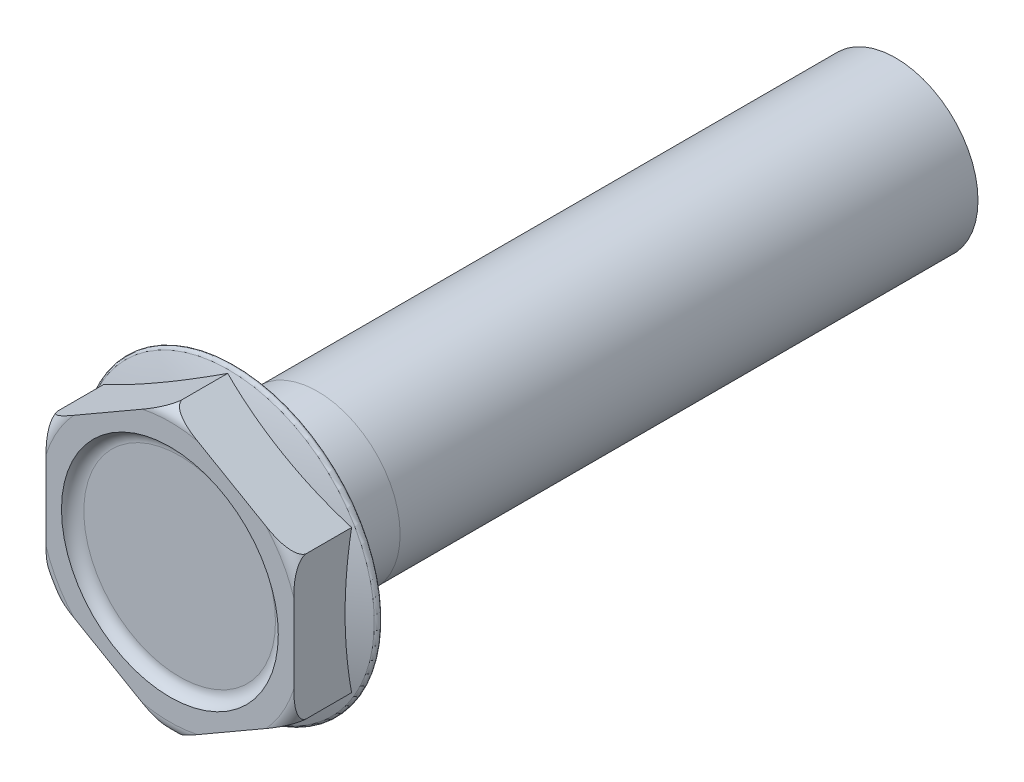
SolidWorks part; units mm, degrees
note: '?' marks a value the reader was unsure of.
extrude "Shank" add sketch "Shank Sketch" against normal blind 101.6
sketch "Shank Sketch" plane through (0, 0, 0) normal (0, 0, 1) x (1, 0, 0)
  line L0 (50, 0) -> (-50, 0) construction
  line L1 (0, -50) -> (0, 50) construction
  circle A0 centre (0, 0) radius 12.7
  dimension "Shank diameter" = 25.4
extrude "Head" add sketch "Head Sketch" along normal blind 10
sketch "Head Sketch" plane through (0, 0, 0) normal (0, 0, 1) x (1, 0, 0)
  line L0 (0, 21.997) -> (19.05, 10.9985)
  line L1 (19.05, 10.9985) -> (19.05, -10.9985)
  line L2 (19.05, -10.9985) -> (0, -21.997)
  line L3 (0, -21.997) -> (-19.05, -10.9985)
  line L4 (-19.05, -10.9985) -> (-19.05, 10.9985)
  line L5 (-19.05, 10.9985) -> (0, 21.997)
  line L6 (19.05, 10.9985) -> (-19.05, -10.9985) construction
  line L7 (0, 21.997) -> (0, -21.997) construction
  line L8 (-19.05, 10.9985) -> (19.05, -10.9985) construction
  point P0 (0, 0)
  dimension "D1" = 60
  dimension "D2" = 60
  dimension "Width across flats" = 38.1
ref_plane "Plane1" through (0, 0, 0) normal (0, 0, 1) x (1, 0, 0)
ref_plane "Plane2" through (0, 0, 0) normal (0, 1, 0) x (-1, 0, 0)
ref_plane "Plane3" through (0, 0, 0) normal (1, 0, 0) x (0, 0, -1)
other "Configuration Table"
sketch "Sketch3" plane through (0, 0, 0) normal (0, 1, 0) x (-1, 0, 0)
  line L0 (0, 0) -> (0, 10) construction
  line L1 (0, -101.6) -> (0, 0) construction
  line L4 (-22.225, 0) -> (0, 0)
  line L5 (0, 0) -> (0, 5)
  arc A0 (0, 5) -> (-22.3993, 0.9686) centre (0, -59.2438) ccw
  arc A1 (-22.225, 0) -> (-22.3993, 0.9686) centre (-22.225, 0.5) cw
  dimension "D1" = 0.5
  dimension "D2" = 44.45
  dimension "D3" = 5
revolve "Flange" add sketch "Sketch3" angle 360 about L0
ref_axis "Axis1" through (0, 0, -151.6) along (0, 0, 1)?
sketch "Sketch5" plane through (0, 0, 0) normal (1, 0, 0) x (0, 0, -1)
  line L0 (-10, -19.997) -> (-10, -21.997)
  line L1 (-10, -21.997) -> (-8, -21.997)
  line L2 (-10, -21.997) -> (-1.1168, -21.997) construction
  line L3 (-10, -21.997) -> (-10, -10.9985) construction
  line L5 (-15.0856, 0) -> (-8.1394, 0) construction
  line L6 (50, 0) -> (-50, 0) construction
  arc A0 (-10, -19.997) -> (-8, -21.997) centre (-8, -19.997) ccw
  dimension "D1" = 2
revolve "Head Trim" cut sketch "Sketch5" angle 360 about L5
sketch "Sketch6" plane through (0, 0, 10) normal (0, 0, 1) x (1, 0, 0)
  circle A3 centre (0, 0) radius 16.6687
  dimension "D1" = 33.3375
extrude "Head Cut" cut sketch "Sketch6" against normal blind 1.5
fillet "Fillet1" radius 2 1 edges at (16.6687, 0, 8.5)
fillet "Fillet2" radius 0.5 1 edges at (12.7, 0, 0)
sketch "Thread End" plane through (0, 0, 0) normal (1, 0, 0) x (0, 0, -1)
  line L0 (12.7, 12.7) -> (12.7, 12.65)
  line L1 (101.6, 12.7) -> (0.5, 12.7) construction
  line L2 (12.7, 12.65) -> (101.6, 12.65)
  line L3 (101.6, 12.7) -> (12.7, 12.7)
  line L4 (21.5519, 0) -> (27.4271, 0) construction
  line L5 (101.6, 0) -> (0.5, 0) construction
  line L6 (101.6, -12.7) -> (101.6, 12.7) construction
  line L7 (101.6, 12.65) -> (101.6, 12.7)
  dimension "D1" = 0.05
  dimension "Length of thread" = 88.9
revolve "Thread Cut" cut sketch "Thread End" angle 360 about L4
cosmetic thread "Cosmetic Thread2" parameters "D2"=11
equation "\"D1@Sketch6\" = \"Width across flats@Head Sketch\"*7/8"
